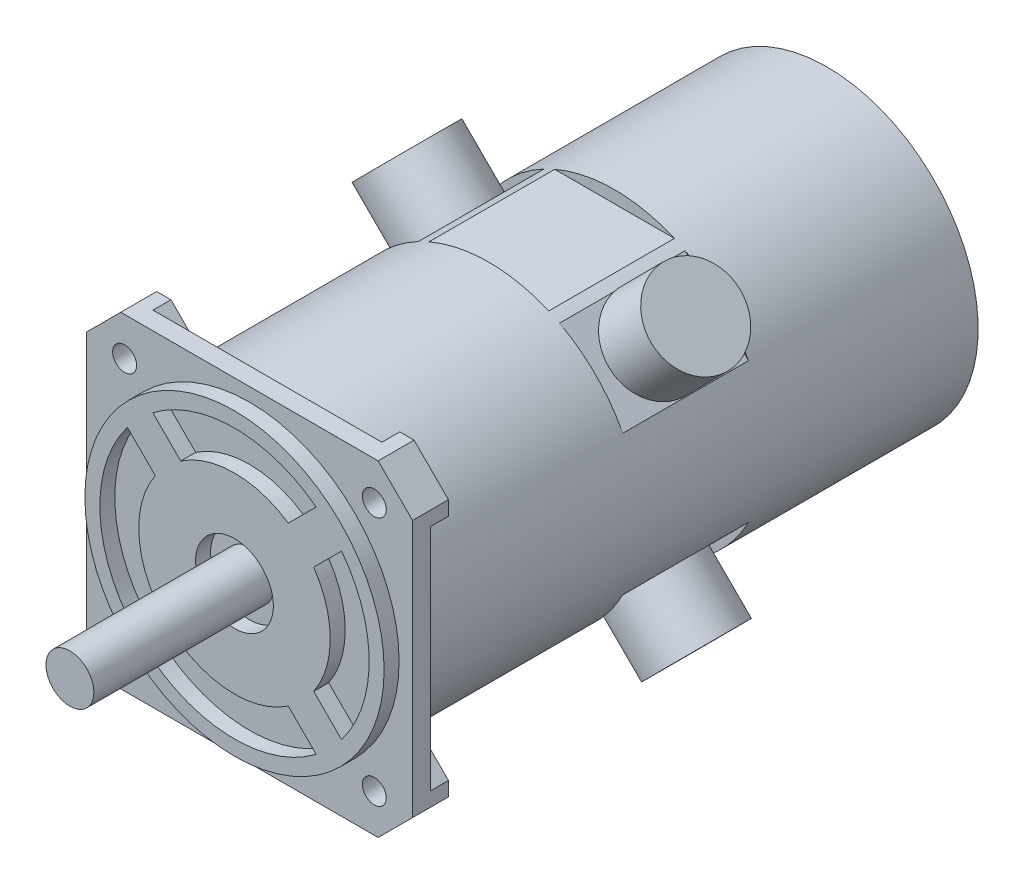
SolidWorks part; units mm, degrees
ref_plane "Front Plane" through (0, 0, 0) normal (0, 0, 1) x (1, 0, 0)
ref_plane "Top Plane" through (0, 0, 0) normal (0, 1, 0) x (1, 0, 0)
ref_plane "Right Plane" through (0, 0, 0) normal (1, 0, 0) x (0, 0, -1)
sketch "Sketch1" plane through (0, 0, 0) normal (0, 0, 1) x (1, 0, 0)
  line L0 (0, 27.25) -> (0, -27.25) construction
  line L1 (-21.5, 27.25) -> (21.5, 27.25)
  line L2 (-27.25, 21.5) -> (-27.25, -21.5)
  line L3 (-21.5, -27.25) -> (21.5, -27.25)
  line L4 (27.25, 21.5) -> (27.25, -21.5)
  line L5 (-21.5, 27.25) -> (-27.25, 21.5)
  line L6 (21.5, 27.25) -> (27.25, 21.5)
  line L7 (-27.25, -21.5) -> (-21.5, -27.25)
  line L8 (21.5, -27.25) -> (27.25, -21.5)
  line L9 (-27.25, 0) -> (27.25, 0) construction
  line L10 (24.375, 24.375) -> (-24.375, -24.375) construction
  line L11 (-24.375, 24.375) -> (24.375, -24.375) construction
  circle A0 centre (0, 0) radius 25
  circle A1 centre (0, 0) radius 16
  circle A2 centre (0, 0) radius 4
  circle A3 centre (20.8597, 20.8597) radius 2
  circle A4 centre (-20.8597, 20.8597) radius 2
  circle A5 centre (-20.8597, -20.8597) radius 2
  circle A6 centre (20.8597, -20.8597) radius 2
  dimension "D1" = 50
  dimension "D2" = 32
  dimension "D3" = 8
  dimension "D7" = 4
  dimension "D8" = 55
  dimension "D4" = 54.5
  dimension "D5" = 43
  dimension "D6" = 135
extrude "Boss-Extrude1" add sketch "Sketch1" against normal blind 6 contours L1 L6 L4 L8 L3 L7 L2 L5 | A3 | A4 | A5 | A6
sketch "Sketch2" plane through (0, 0, 0) normal (0, 0, 1) x (1, 0, 0)
  line L0 (-17.8892, 13.6465) -> (-13.2344, 8.9917)
  line L1 (-13.6465, 17.8892) -> (-8.9917, 13.2344)
  line L2 (13.6465, 17.8892) -> (8.9917, 13.2344)
  line L3 (17.8892, 13.6465) -> (13.2344, 8.9917)
  line L4 (13.2344, -8.9917) -> (17.8892, -13.6465)
  line L5 (8.9917, -13.2344) -> (13.6465, -17.8892)
  line L6 (-8.9917, -13.2344) -> (-13.6465, -17.8892)
  line L7 (-13.2344, -8.9917) -> (-17.8892, -13.6465)
  line L8 (20.8597, -20.8597) -> (-20.8597, 20.8597) construction
  line L9 (-20.8597, -20.8597) -> (20.8597, 20.8597) construction
  circle A0 centre (0, 0) radius 25 construction
  circle A1 centre (0, 0) radius 25
  circle A2 centre (0, 0) radius 16 construction
  arc A3 (-13.2344, 8.9917) -> (-13.2344, -8.9917) centre (0, 0) ccw
  circle A4 centre (0, 0) radius 6.5
  arc A5 (-17.8892, 13.6465) -> (-17.8892, -13.6465) centre (0, 0) ccw
  arc A6 (13.6465, 17.8892) -> (-13.6465, 17.8892) centre (0, 0) ccw
  arc A7 (8.9917, 13.2344) -> (-8.9917, 13.2344) centre (0, 0) ccw
  arc A8 (13.2344, -8.9917) -> (13.2344, 8.9917) centre (0, 0) ccw
  arc A9 (17.8892, -13.6465) -> (17.8892, 13.6465) centre (0, 0) ccw
  arc A10 (-8.9917, -13.2344) -> (8.9917, -13.2344) centre (0, 0) ccw
  arc A11 (-13.6465, -17.8892) -> (13.6465, -17.8892) centre (0, 0) ccw
  dimension "D1" = 13
  dimension "D2" = 45
  dimension "D3" = 6
  dimension "D4" = 6
  dimension "D5" = 6
  dimension "D6" = 6
extrude "Boss-Extrude2" add sketch "Sketch2" along normal blind 2.5
extrude "Boss-Extrude3" add sketch "Sketch1<3>" along normal blind 30 contours A2
sketch "Sketch1<3>" plane through (0, 0, 0) normal (0, 0, 1) x (1, 0, 0) same geometry as "Sketch1"
sketch "Sketch3" plane through (0, 0, -6) normal (0, 0, -1) x (-1, 0, 0)
  line L0 (19.1183, 27.25) -> (13.3195, 21.4512)
  line L1 (24.375, 24.375) -> (-24.375, -24.375) construction
  line L2 (-24.375, 24.375) -> (24.375, -24.375) construction
  line L3 (27.25, 19.1183) -> (21.4512, 13.3195)
  line L4 (-19.1183, 27.25) -> (-13.3195, 21.4512)
  line L5 (-27.25, 19.1183) -> (-21.4512, 13.3195)
  line L6 (-27.25, -19.1183) -> (-21.4512, -13.3195)
  line L7 (-19.1183, -27.25) -> (-13.3195, -21.4512)
  line L8 (27.25, 21.5) -> (21.5, 27.25)
  line L9 (21.5, 27.25) -> (-21.5, 27.25)
  line L10 (-21.5, 27.25) -> (-27.25, 21.5)
  line L11 (-27.25, 21.5) -> (-27.25, -21.5)
  line L12 (-27.25, -21.5) -> (-21.5, -27.25)
  line L13 (-21.5, -27.25) -> (21.5, -27.25)
  line L14 (21.5, -27.25) -> (27.25, -21.5)
  line L15 (27.25, -21.5) -> (27.25, 21.5)
  line L17 (19.1183, 27.25) -> (-19.1183, 27.25)
  line L19 (-27.25, 19.1183) -> (-27.25, -19.1183)
  line L21 (-19.1183, -27.25) -> (19.1183, -27.25)
  line L23 (27.25, -19.1183) -> (27.25, 19.1183)
  line L24 (27.25, -19.1183) -> (21.4512, -13.3195)
  line L25 (19.1183, -27.25) -> (13.3195, -21.4512)
  line L26 (-27.25, 21.5) -> (-27.25, -21.5) construction
  arc A0 (13.3195, 21.4512) -> (-13.3195, 21.4512) centre (0, 0) ccw
  arc A1 (21.4512, -13.3195) -> (21.4512, 13.3195) centre (0, 0) ccw
  arc A2 (-13.3195, -21.4512) -> (13.3195, -21.4512) centre (0, 0) ccw
  arc A3 (-21.4512, 13.3195) -> (-21.4512, -13.3195) centre (0, 0) ccw
  dimension "D1" = 50.5
  dimension "D3" = 11.5
  dimension "D4" = 11.5
  dimension "D5" = 11.5
  dimension "D6" = 11.5
  dimension "D2" = 0
extrude "Cut-Extrude1" cut sketch "Sketch3" against normal blind 3
sketch "Sketch5" plane through (0, 0, -6) normal (0, 0, -1) x (-1, 0, 0)
  circle A0 centre (0, 0) radius 25.25
  dimension "D1" = 50.5
extrude "Boss-Extrude4" add sketch "Sketch5" along normal blind 34
sketch "Sketch6" plane through (0, 0, -40) normal (0, 0, -1) x (-1, 0, 0)
  line L0 (-10, 23.1854) -> (10, 23.1854)
  line L1 (11.8037, 22.3212) -> (22.3825, 11.6869)
  line L2 (-11.8037, 22.3212) -> (-22.3825, 11.6869)
  line L3 (0, 0) -> (0, 25.25) construction
  line L4 (-25.25, 0) -> (25.25, 0) construction
  line L5 (11.8037, -22.3212) -> (22.3825, -11.6869)
  line L6 (-10, -23.1854) -> (10, -23.1854)
  line L7 (-11.8037, -22.3212) -> (-22.3825, -11.6869)
  circle A0 centre (0, 0) radius 25.25 construction
  arc A1 (-22.3825, 11.6869) -> (-22.3825, -11.6869) centre (0, 0) ccw
  arc A2 (-10, 23.1854) -> (-11.8037, 22.3212) centre (0, 0) ccw
  arc A3 (11.8037, 22.3212) -> (10, 23.1854) centre (0, 0) ccw
  arc A4 (22.3825, -11.6869) -> (22.3825, 11.6869) centre (0, 0) ccw
  arc A5 (10, -23.1854) -> (11.8037, -22.3212) centre (0, 0) ccw
  arc A6 (-11.8037, -22.3212) -> (-10, -23.1854) centre (0, 0) ccw
  arc A7 (13.3195, 21.4512) -> (-13.3195, 21.4512) centre (0, 0) ccw construction
  dimension "D1" = 20
  dimension "D2" = 15
  dimension "D3" = 2
extrude "Boss-Extrude5" add sketch "Sketch6" along normal blind 21
sketch "Sketch7" plane through (0, 0, -61) normal (0, 0, -1) x (-1, 0, 0)
  circle A0 centre (0, 0) radius 25.25
  dimension "D1" = 50.5
extrude "Boss-Extrude6" add sketch "Sketch7" along normal blind 35.5
sketch "Sketch8" plane through (-17.0931, 17.0041, 0) normal (-0.709, 0.7053, 0) x (0.7053, 0.709, 0)
  line L0 (0, 61) -> (0, 40) construction
  line L1 (-7.5, 61) -> (7.5, 61) construction
  line L2 (7.5, 40) -> (-7.5, 40) construction
  circle A0 centre (0, 50.5) radius 7.5
  dimension "D1" = 15
extrude "Boss-Extrude7" add sketch "Sketch8" along normal blind 10
pattern_circular "CirPattern1" count 4 over 360 about axis through (0, 0, -3) along (0, 0, -1) of "Boss-Extrude7"
sketch "Sketch10" plane through (0, 0, 0) normal (1, 0, 0) x (0, 0, -1)
  line B0 (-2.5, 4) -> (-30, 4)
  line B1 (-30, 4) -> (-30, -4)
  line B2 (-30, -4) -> (-2.5, -4)
  line B3 (-2.5, 25) -> (-2.5, -25)
  line B4 (0, 25) -> (-2.5, 25)
  line B5 (0, 27.25) -> (0, 25)
  line B6 (6, 27.25) -> (0, 27.25)
  line B7 (6, 27.25) -> (6, 25.25)
  line B8 (40, 25.25) -> (6, 25.25)
  line B9 (96.5, 25.25) -> (61, 25.25)
  line B10 (96.5, -25.25) -> (96.5, 25.25)
  line B11 (61, -25.25) -> (96.5, -25.25)
  line B12 (6, -25.25) -> (40, -25.25)
  line B13 (-2.5, -25) -> (0, -25)
  line B14 (0, -25) -> (0, -27.25)
  line B15 (0, -27.25) -> (6, -27.25)
  line B16 (6, -27.25) -> (6, -25.25)
  line B17 (40, -25.25) -> (40, -23.1854)
  line B18 (40, -23.1854) -> (43.1014, -23.1854)
  line B19 (61, -25.25) -> (61, -23.1854)
  line B20 (61, -23.1854) -> (57.8986, -23.1854)
  line B21 (40, 25.25) -> (40, 23.1854)
  line B22 (40, 23.1854) -> (43.1345, 23.1854)
  line B23 (61, 25.25) -> (61, 23.1854)
  line B24 (61, 23.1854) -> (57.8655, 23.1854)
  line B25 (-30, 0) -> (96.5, 0) construction
  ellipse B26 centre (50.5, 24.1826) end of major axis (58, 24.1826) minor radius 5.2894
  ellipse B27 centre (50.5, -24.0567) end of major axis (43, -24.0567) minor radius 5.3171
sketch_block_instance "Block2-1"
sketch_block "Block2"
